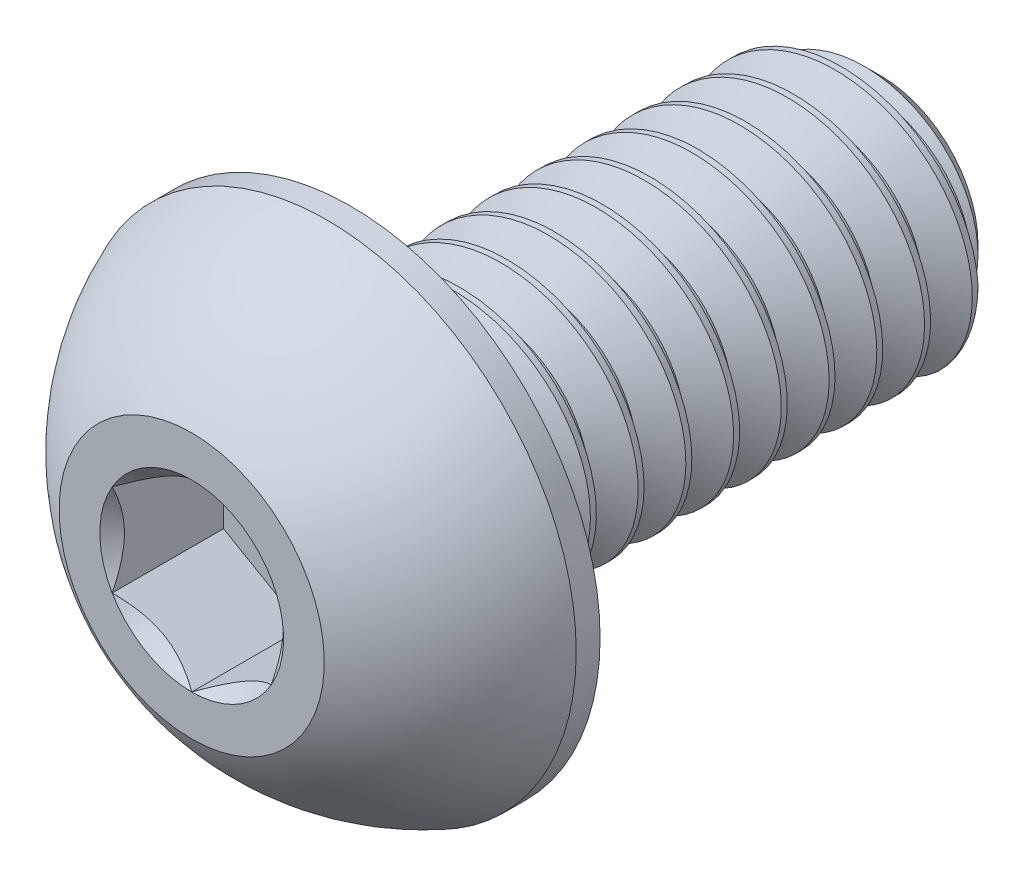
SolidWorks part; units mm, degrees
ref_plane "Front" through (0, 0, 0) normal (0, 0, 1) x (1, 0, 0)
ref_plane "Top" through (0, 0, 0) normal (0, 1, 0) x (1, 0, 0)
ref_plane "Right" through (0, 0, 0) normal (1, 0, 0) x (0, 0, -1)
sketch "Sketch1" plane through (0, 0, 0) normal (1, 0, 0) x (0, 0, -1)
  line L2 (1.5, 1.25) -> (6.5, 1.25)
  line L3 (6.5, 1.25) -> (6.5, 0)
  line L4 (6.5, 0) -> (1.5, 0)
  line L6 (1.275, 2.35) -> (1.5, 2.35) construction
  line L7 (6.5, 1.25) -> (6.5, -1.25) construction
  line L8 (0, 0) -> (1.5, 0) construction
  line L9 (1.5, 2.35) -> (1.5, -2.35) construction
  line L11 (1.5, 1.25) -> (1.5, 0)
  line L13 (0, 0.75) -> (0, -0.75) construction
  line L14 (0, 0.75) -> (0, 1.25) construction
  line L15 (6.5, -1.25) -> (6.05, -1.25) construction
  arc A3 (0, 1.25) -> (1.275, 2.35) centre (2.1904, 0) cw construction
  dimension "D1" = 0.225
  dimension "Pitch" = 0.45
revolve "Revolve1" add sketch "Sketch1" angle 360 mid plane about L4
sketch "Sketch7" plane through (0, 0, 0) normal (1, 0, 0) x (0, 0, -1)
  line L6 (1.275, 2.35) -> (1.5, 2.35) construction
  line L8 (0, 0) -> (1.5, 0) construction
  line L11 (1.5, 2.35) -> (1.5, -2.35) construction
  line L12 (1.275, 2.35) -> (1.5, 2.35)
  line L13 (0, 0) -> (1.5, 0)
  line L14 (0, 0.75) -> (0, -0.75) construction
  line L15 (1.5, 2.35) -> (1.5, 0)
  line L16 (0, 1.25) -> (0, 0)
  arc A2 (1.275, 2.35) -> (0, 1.25) centre (2.1904, 0) ccw construction
  arc A3 (1.275, 2.35) -> (0, 1.25) centre (2.1904, 0) ccw
revolve "Revolve2" add sketch "Sketch7" angle 360 mid plane about L13
sketch "Sketch5" plane through (0, 0, 0) normal (0, 0, 1) x (1, 0, 0)
  line L1 (0.75, -0.433) -> (0.75, 0.433)
  line L2 (0.75, 0.433) -> (0, 0.866)
  line L3 (0, 0.866) -> (-0.75, 0.433)
  line L4 (-0.75, 0.433) -> (-0.75, -0.433)
  line L5 (-0.75, -0.433) -> (0, -0.866)
  line L6 (0, -0.866) -> (0.75, -0.433)
  circle A0 centre (0, 0) radius 0.75 construction
extrude "Cut-Extrude2" cut sketch "Sketch5" against normal blind 1.05
sketch "Sketch6" plane through (0, 0, 0) normal (0, 0, 1) x (1, 0, 0)
  circle A0 centre (0, 0) radius 0.866
extrude "Cut-Extrude3" cut sketch "Sketch6" against normal blind 1.05 draft 45
sketch "Sketch11" plane through (0, 0, 0) normal (1, 0, 0) x (0, 0, -1)
  line L0 (1.5, -2.35) -> (1.5, 2.35)
  point P4 (1.5, 0)
split "Split1" trim tools "Sketch11" bodies to split 113 resulting bodies 119 120
sketch "Sketch10" plane through (0, 0, 0) normal (1, 0, 0) x (0, 0, -1)
  line L0 (6.5, 1.25) -> (6.5, -1.25) construction
  point P0 (5.825, -1.25)
  dimension "D1" = 0.675
sketch "Sketch3" plane through (0, 0, -6.5) normal (0, 0, -1) x (-1, 0, 0)
  circle A0 centre (0, 0) radius 1.25
curve "Helix/Spiral1" pitch 0.45 height 5.45 radius 1.25 centre (0, 0, -6.5) axis (0, 0, 1) start towards (0, 1, 0)
sketch "Sketch2" plane through (0, 0, 0) normal (1, 0, 0) x (0, 0, -1)
  line L0 (6.4719, 1.2987) -> (6.9219, 1.2987) construction
  line L1 (6.9219, 1.2987) -> (6.6969, 0.909) construction
  line L2 (6.6969, 0.909) -> (6.4719, 1.2987) construction
  line L3 (6.6969, 1.2987) -> (6.6969, 1.25) construction
  line L4 (6.6969, 1.25) -> (6.6969, 0.9577) construction
  line L5 (6.6969, 0.9577) -> (6.6969, 0.909) construction
  line L6 (6.6687, 0.9577) -> (6.725, 0.9577)
  line L7 (6.5, 1.25) -> (6.8937, 1.25) construction
  line L8 (6.4859, 1.2744) -> (6.9078, 1.2744)
  line L9 (6.4859, 1.2744) -> (6.6687, 0.9577)
  line L10 (6.9078, 1.2744) -> (6.725, 0.9577)
  point P10 (6.6969, 0.9577)
  point P13 (6.6969, 1.25)
  point P16 (6.6969, 1.2744)
  dimension "D1" = 0.45
  dimension "D2" = 0.0563
chamfer "Chamfer1" distance 0.3375 angle 45 1 edges at (0, 1.25, -6.5)
sweep "Cut-Sweep1" cut profiles "Sketch2" path "Helix/Spiral1" align with end faces yes
combine bodies "Combine1" operation type add bodies to combine 120 114
equation "\"D3@Helix/Spiral1\" = \"Lg@Sketch1\" + \"D4@Helix/Spiral1\""
equation "\"D1@Chamfer1\" = \"D4@Helix/Spiral1\" * .75"
equation "\"D1@Cut-Extrude2\" = \"Head Ht@Sketch1\" * .7"
equation "\"D1@Sketch1\" = \"Head Ht@Sketch1\" * .15"
equation "\"D1@Sketch10\" = \"D4@Helix/Spiral1\" * 1.5"
equation "\"D1@Cut-Extrude3\" = \"D1@Cut-Extrude2\""
equation "\"D4@Helix/Spiral1\"=\"Pitch@Sketch1\""
equation "\"D1@Sketch2\"=\"Pitch@Sketch1\""
equation "\"D2@Sketch2\"=\"D1@Sketch2\"/8"
